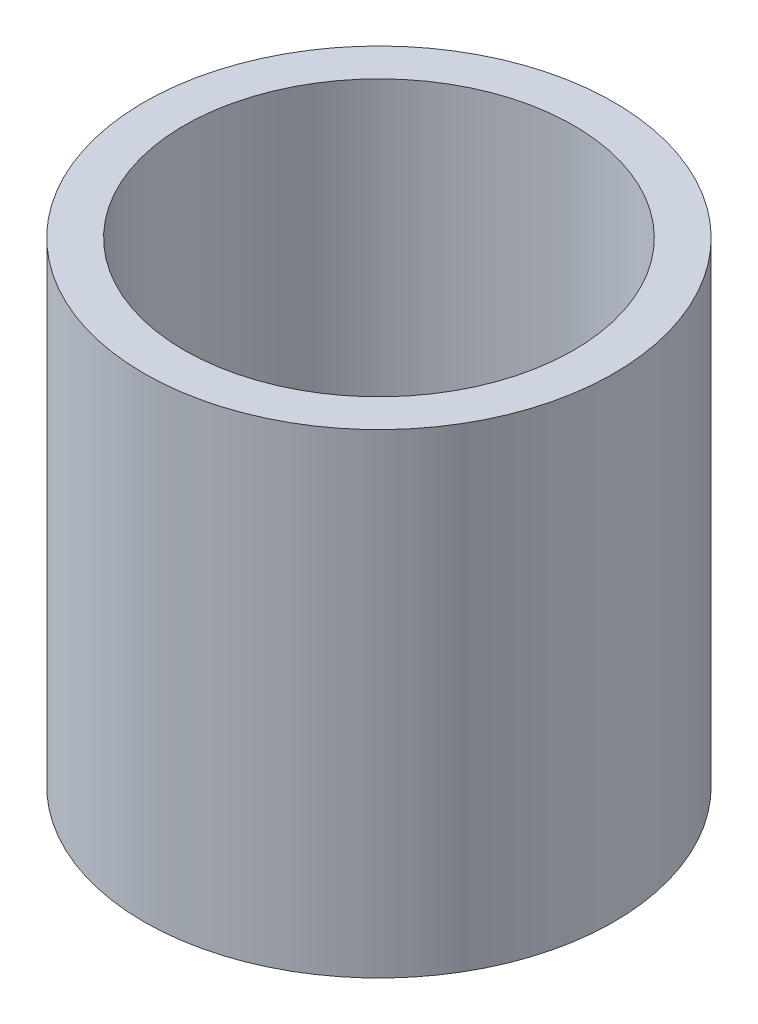
SolidWorks part; units mm, degrees
ref_plane "Front Plane" through (0, 0, 0) normal (0, 0, 1) x (1, 0, 0)
ref_plane "Top Plane" through (0, 0, 0) normal (0, 1, 0) x (1, 0, 0)
ref_plane "Right Plane" through (0, 0, 0) normal (1, 0, 0) x (0, 0, -1)
sketch "Sketch1" plane through (0, 0, 0) normal (0, 1, 0) x (1, 0, 0)
  circle A0 centre (0, 0) radius 17.5
  dimension "SLEEVE_OD" = 35
extrude "Boss-Extrude1" add sketch "Sketch1" along normal blind 35.3782
sketch "Sketch2" plane through (0, 0, 0) normal (0, 1, 0) x (1, 0, 0)
  circle A0 centre (0, 0) radius 14.505
  dimension "BORE_D" = 29.0099
extrude "Cut-Extrude1" cut sketch "Sketch2" along normal through all
chamfer "Chamfer1" distance 3.098 angle 30 rebuild error yes
